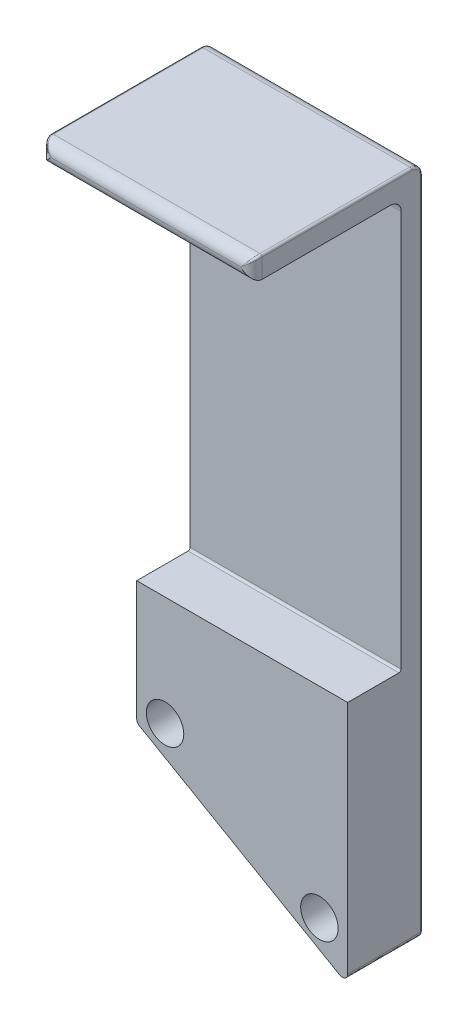
SolidWorks part; units mm, degrees
ref_plane "Front Plane" through (0, 0, 0) normal (0, 0, 1) x (1, 0, 0)
ref_plane "Top Plane" through (0, 0, 0) normal (0, 1, 0) x (1, 0, 0)
ref_plane "Right Plane" through (0, 0, 0) normal (1, 0, 0) x (0, 0, -1)
sketch "Model" plane through (0, 0, 0) normal (0, 0, 1) x (1, 0, 0)
  line L0 (-21.8431, 7.4481) -> (-8.6148, 30.3792)
  line L1 (-38.0636, 15.3297) -> (-23.771, 7.0696)
  line L2 (-75.3888, 20.2293) -> (-38.7189, 15.4592)
  line L3 (-86.2854, 34.8343) -> (-75.7419, 20.3766)
  line L4 (-29.1405, 92.9799) -> (-29.1405, 91.7303)
  line L5 (-8.8891, 91.2299) -> (-28.6402, 91.2299)
  line L6 (-8.3888, 90.7295) -> (-8.3888, 31.2555)
  line L7 (-86.6385, 34.9791) -> (-141.6396, 34.9791)
  line L8 (-142.1399, 90.7295) -> (-142.1399, 35.4795)
  line L9 (-104.6394, 91.2299) -> (-141.6396, 91.2299)
  line L10 (-104.139, 95.4793) -> (-104.139, 91.7303)
  line L11 (-85.6402, 95.9797) -> (-103.6387, 95.9797)
  line L12 (-85.1399, 97.7297) -> (-85.1399, 96.4801)
  line L13 (-67.6393, 98.2301) -> (-84.6395, 98.2301)
  line L14 (-67.1389, 96.4801) -> (-67.1389, 97.7297)
  line L15 (-48.6401, 95.9797) -> (-66.6385, 95.9797)
  line L16 (-48.1397, 93.9807) -> (-48.1397, 95.4793)
  line L17 (-29.6384, 93.4803) -> (-47.6393, 93.4803)
  line L18 (135.1563, 30.6526) -> (116.2359, 41.5721)
  line L19 (123.1828, 7.2669) -> (135.5373, 28.7222)
  line L20 (106.9623, 15.1485) -> (121.2549, 6.8884)
  line L21 (69.6371, 20.0481) -> (106.307, 15.278)
  line L22 (58.7405, 34.6531) -> (69.284, 20.1955)
  line L23 (115.8854, 92.7987) -> (115.8828, 42.2376)
  line L24 (58.3874, 34.7979) -> (3.3863, 34.7979)
  line L25 (2.886, 90.5483) -> (2.886, 35.2983)
  line L26 (40.3865, 91.0487) -> (3.3863, 91.0487)
  line L27 (40.8869, 95.2981) -> (40.8869, 91.5491)
  line L28 (59.3857, 95.7985) -> (41.3872, 95.7985)
  line L29 (59.886, 97.5485) -> (59.886, 96.2989)
  line L30 (77.3866, 98.0489) -> (60.3864, 98.0489)
  line L31 (77.887, 96.2989) -> (77.887, 97.5485)
  line L32 (96.3858, 95.7985) -> (78.3874, 95.7985)
  line L33 (96.8862, 93.7995) -> (96.8862, 95.2981)
  line L34 (115.3875, 93.2991) -> (97.3866, 93.2991)
  line L35 (20.1915, -96.2476) -> (6.9631, -73.3165)
  line L36 (36.4119, -88.366) -> (22.1193, -96.6261)
  line L37 (73.7371, -83.4663) -> (37.0672, -88.2365)
  line L38 (84.6337, -68.8614) -> (74.0902, -83.319)
  line L39 (27.4889, -10.7157) -> (27.4889, -11.9654)
  line L40 (7.2375, -12.4658) -> (26.9885, -12.4658)
  line L41 (6.7371, -12.9662) -> (6.7371, -72.4402)
  line L42 (84.9868, -68.7166) -> (139.9879, -68.7166)
  line L43 (140.4883, -12.9662) -> (140.4883, -68.2162)
  line L44 (102.9878, -12.4658) -> (139.9879, -12.4658)
  line L45 (102.4874, -8.2164) -> (102.4874, -11.9654)
  line L46 (83.9886, -7.716) -> (101.987, -7.716)
  line L47 (83.4882, -5.9659) -> (83.4882, -7.2156)
  line L48 (65.9876, -5.4656) -> (82.9878, -5.4656)
  line L49 (65.4872, -7.2156) -> (65.4872, -5.9659)
  line L50 (46.9884, -7.716) -> (64.9869, -7.716)
  line L51 (46.488, -9.715) -> (46.488, -8.2164)
  line L52 (27.9867, -10.2154) -> (45.9877, -10.2154)
  line L53 (-136.808, -73.043) -> (-117.8876, -62.1236)
  line L54 (-124.8344, -96.4288) -> (-137.189, -74.9734)
  line L55 (-108.614, -88.5472) -> (-122.9066, -96.8073)
  line L56 (-71.2888, -83.6475) -> (-107.9587, -88.4176)
  line L57 (-60.3922, -69.0425) -> (-70.9357, -83.5002)
  line L58 (-117.537, -10.8969) -> (-117.5345, -61.4581)
  line L59 (-60.0391, -68.8978) -> (-5.038, -68.8978)
  line L60 (-4.5376, -13.1474) -> (-4.5376, -68.3974)
  line L61 (-42.0381, -12.647) -> (-5.038, -12.647)
  line L62 (-42.5385, -8.3976) -> (-42.5385, -12.1466)
  line L63 (-61.0373, -7.8972) -> (-43.0389, -7.8972)
  line L64 (-61.5377, -6.1471) -> (-61.5377, -7.3968)
  line L65 (-79.0383, -5.6467) -> (-62.0381, -5.6467)
  line L66 (-79.5387, -7.3968) -> (-79.5387, -6.1471)
  line L67 (-98.0375, -7.8972) -> (-80.039, -7.8972)
  line L68 (-98.5378, -9.8962) -> (-98.5378, -8.3976)
  line L69 (-117.0392, -10.3965) -> (-99.0382, -10.3965)
  line L70 (138.9148, 92.1117) -> (138.9148, 33.3582)
  line L71 (138.1649, 32.9251) -> (119.446, 43.7282)
  line L72 (119.196, 44.1613) -> (119.196, 92.1092)
  line L73 (119.6959, 92.6092) -> (138.4148, 92.6117)
  line L74 (-140.5665, -11.584) -> (-140.5665, -70.3375)
  line L75 (-139.8166, -70.7706) -> (-121.0977, -59.9674)
  line L76 (-120.8476, -59.5344) -> (-120.8476, -11.5865)
  line L77 (-121.3476, -11.0865) -> (-140.0664, -11.084)
  line L78 (18.8966, 74.9256) -> (4.8966, 74.9256)
  line L79 (4.8966, 74.9256) -> (4.8966, 88.9256)
  line L80 (4.8966, 88.9256) -> (18.8966, 88.9256)
  line L81 (18.8966, 88.9256) -> (18.8966, 74.9256)
  line L82 (18.8966, 55.9256) -> (4.8966, 55.9256)
  line L83 (4.8966, 55.9256) -> (4.8966, 69.9256)
  line L84 (4.8966, 69.9256) -> (18.8966, 69.9256)
  line L85 (18.8966, 69.9256) -> (18.8966, 55.9256)
  line L86 (18.8966, 36.9256) -> (4.8966, 36.9256)
  line L87 (4.8966, 36.9256) -> (4.8966, 50.9256)
  line L88 (4.8966, 50.9256) -> (18.8966, 50.9256)
  line L89 (18.8966, 50.9256) -> (18.8966, 36.9256)
  line L90 (37.8948, 74.9262) -> (23.8948, 74.9262)
  line L91 (23.8948, 74.9262) -> (23.8948, 88.9262)
  line L92 (23.8948, 88.9262) -> (37.8948, 88.9262)
  line L93 (37.8948, 88.9262) -> (37.8948, 74.9262)
  line L94 (37.8948, 55.9262) -> (23.8948, 55.9262)
  line L95 (23.8948, 55.9262) -> (23.8948, 69.9262)
  line L96 (23.8948, 69.9262) -> (37.8948, 69.9262)
  line L97 (37.8948, 69.9262) -> (37.8948, 55.9262)
  line L98 (37.8948, 36.9262) -> (23.8948, 36.9262)
  line L99 (23.8948, 36.9262) -> (23.8948, 50.9262)
  line L100 (23.8948, 50.9262) -> (37.8948, 50.9262)
  line L101 (37.8948, 50.9262) -> (37.8948, 36.9262)
  line L102 (56.895, 79.671) -> (42.895, 79.671)
  line L103 (42.895, 79.671) -> (42.895, 93.671)
  line L104 (42.895, 93.671) -> (56.895, 93.671)
  line L105 (56.895, 93.671) -> (56.895, 79.671)
  line L106 (56.895, 60.6711) -> (42.895, 60.6711)
  line L107 (42.895, 60.6711) -> (42.895, 74.6711)
  line L108 (42.895, 74.6711) -> (56.895, 74.6711)
  line L109 (56.895, 74.6711) -> (56.895, 60.6711)
  line L110 (56.895, 41.6711) -> (42.895, 41.6711)
  line L111 (42.895, 41.6711) -> (42.895, 55.6711)
  line L112 (42.895, 55.6711) -> (56.895, 55.6711)
  line L113 (56.895, 55.6711) -> (56.895, 41.6711)
  line L114 (75.897, 82.0499) -> (61.897, 82.0499)
  line L115 (61.897, 82.0499) -> (61.897, 96.0499)
  line L116 (61.897, 96.0499) -> (75.897, 96.0499)
  line L117 (75.897, 96.0499) -> (75.897, 82.0499)
  line L118 (75.897, 63.0499) -> (61.897, 63.0499)
  line L119 (61.897, 63.0499) -> (61.897, 77.0499)
  line L120 (61.897, 77.0499) -> (75.897, 77.0499)
  line L121 (75.897, 77.0499) -> (75.897, 63.0499)
  line L122 (75.897, 44.0499) -> (61.897, 44.0499)
  line L123 (61.897, 44.0499) -> (61.897, 58.0499)
  line L124 (61.897, 58.0499) -> (75.897, 58.0499)
  line L125 (75.897, 58.0499) -> (75.897, 44.0499)
  line L126 (94.8982, 79.6753) -> (80.8982, 79.6753)
  line L127 (80.8982, 79.6753) -> (80.8982, 93.6753)
  line L128 (80.8982, 93.6753) -> (94.8982, 93.6753)
  line L129 (94.8982, 93.6753) -> (94.8982, 79.6753)
  line L130 (94.8982, 60.6753) -> (80.8982, 60.6753)
  line L131 (80.8982, 60.6753) -> (80.8982, 74.6753)
  line L132 (80.8982, 74.6753) -> (94.8982, 74.6753)
  line L133 (94.8982, 74.6753) -> (94.8982, 60.6753)
  line L134 (94.8982, 41.6753) -> (80.8982, 41.6753)
  line L135 (80.8982, 41.6753) -> (80.8982, 55.6753)
  line L136 (80.8982, 55.6753) -> (94.8982, 55.6753)
  line L137 (94.8982, 55.6753) -> (94.8982, 41.6753)
  line L138 (113.9, 77.2905) -> (99.9, 77.2905)
  line L139 (99.9, 77.2905) -> (99.9, 91.2905)
  line L140 (99.9, 91.2905) -> (113.9, 91.2905)
  line L141 (113.9, 91.2905) -> (113.9, 77.2905)
  line L142 (113.9, 58.2905) -> (99.9, 58.2905)
  line L143 (99.9, 58.2905) -> (99.9, 72.2905)
  line L144 (99.9, 72.2905) -> (113.9, 72.2905)
  line L145 (113.9, 72.2905) -> (113.9, 58.2905)
  line L146 (113.9, 39.2905) -> (99.9, 39.2905)
  line L147 (99.9, 39.2905) -> (99.9, 53.2905)
  line L148 (99.9, 53.2905) -> (113.9, 53.2905)
  line L149 (113.9, 53.2905) -> (113.9, 39.2905)
  line L150 (85.4166, 22.0174) -> (71.4166, 22.0174)
  line L151 (71.4166, 22.0174) -> (71.4166, 36.0174)
  line L152 (71.4166, 36.0174) -> (85.4166, 36.0174)
  line L153 (85.4166, 36.0174) -> (85.4166, 22.0174)
  line L154 (104.3289, 17.734) -> (90.806, 21.3575)
  line L155 (90.806, 21.3575) -> (94.4294, 34.8805)
  line L156 (94.4294, 34.8805) -> (107.9524, 31.257)
  line L157 (107.9524, 31.257) -> (104.3289, 17.734)
  line L158 (124.1994, 13.0049) -> (112.075, 20.0049)
  line L159 (112.075, 20.0049) -> (119.075, 32.1293)
  line L160 (119.075, 32.1293) -> (131.1994, 25.1293)
  line L161 (131.1994, 25.1293) -> (124.1994, 13.0049)
  line L162 (-20.5483, -28.7701) -> (-6.5483, -28.7701)
  line L163 (-6.5483, -28.7701) -> (-6.5483, -14.7701)
  line L164 (-6.5483, -14.7701) -> (-20.5483, -14.7701)
  line L165 (-20.5483, -14.7701) -> (-20.5483, -28.7701)
  line L166 (-20.5483, -47.7701) -> (-6.5483, -47.7701)
  line L167 (-6.5483, -47.7701) -> (-6.5483, -33.7701)
  line L168 (-6.5483, -33.7701) -> (-20.5483, -33.7701)
  line L169 (-20.5483, -33.7701) -> (-20.5483, -47.7701)
  line L170 (-20.5483, -66.7701) -> (-6.5483, -66.7701)
  line L171 (-6.5483, -66.7701) -> (-6.5483, -52.7701)
  line L172 (-6.5483, -52.7701) -> (-20.5483, -52.7701)
  line L173 (-20.5483, -52.7701) -> (-20.5483, -66.7701)
  line L174 (-39.5464, -28.7694) -> (-25.5464, -28.7694)
  line L175 (-25.5464, -28.7694) -> (-25.5464, -14.7694)
  line L176 (-25.5464, -14.7694) -> (-39.5464, -14.7694)
  line L177 (-39.5464, -14.7694) -> (-39.5464, -28.7694)
  line L178 (-39.5464, -47.7694) -> (-25.5464, -47.7694)
  line L179 (-25.5464, -47.7694) -> (-25.5464, -33.7694)
  line L180 (-25.5464, -33.7694) -> (-39.5464, -33.7694)
  line L181 (-39.5464, -33.7694) -> (-39.5464, -47.7694)
  line L182 (-39.5464, -66.7694) -> (-25.5464, -66.7694)
  line L183 (-25.5464, -66.7694) -> (-25.5464, -52.7694)
  line L184 (-25.5464, -52.7694) -> (-39.5464, -52.7694)
  line L185 (-39.5464, -52.7694) -> (-39.5464, -66.7694)
  line L186 (-58.5467, -24.0246) -> (-44.5467, -24.0246)
  line L187 (-44.5467, -24.0246) -> (-44.5467, -10.0246)
  line L188 (-44.5467, -10.0246) -> (-58.5467, -10.0246)
  line L189 (-58.5467, -10.0246) -> (-58.5467, -24.0246)
  line L190 (-58.5467, -43.0246) -> (-44.5467, -43.0246)
  line L191 (-44.5467, -43.0246) -> (-44.5467, -29.0246)
  line L192 (-44.5467, -29.0246) -> (-58.5467, -29.0246)
  line L193 (-58.5467, -29.0246) -> (-58.5467, -43.0246)
  line L194 (-58.5467, -62.0246) -> (-44.5467, -62.0246)
  line L195 (-44.5467, -62.0246) -> (-44.5467, -48.0246)
  line L196 (-44.5467, -48.0246) -> (-58.5467, -48.0246)
  line L197 (-58.5467, -48.0246) -> (-58.5467, -62.0246)
  line L198 (-77.5486, -21.6458) -> (-63.5486, -21.6458)
  line L199 (-63.5486, -21.6458) -> (-63.5486, -7.6458)
  line L200 (-63.5486, -7.6458) -> (-77.5486, -7.6458)
  line L201 (-77.5486, -7.6458) -> (-77.5486, -21.6458)
  line L202 (-77.5486, -40.6458) -> (-63.5486, -40.6458)
  line L203 (-63.5486, -40.6458) -> (-63.5486, -26.6458)
  line L204 (-63.5486, -26.6458) -> (-77.5486, -26.6458)
  line L205 (-77.5486, -26.6458) -> (-77.5486, -40.6458)
  line L206 (-77.5486, -59.6458) -> (-63.5486, -59.6458)
  line L207 (-63.5486, -59.6458) -> (-63.5486, -45.6458)
  line L208 (-63.5486, -45.6458) -> (-77.5486, -45.6458)
  line L209 (-77.5486, -45.6458) -> (-77.5486, -59.6458)
  line L210 (-96.5499, -24.0204) -> (-82.5499, -24.0204)
  line L211 (-82.5499, -24.0204) -> (-82.5499, -10.0204)
  line L212 (-82.5499, -10.0204) -> (-96.5499, -10.0204)
  line L213 (-96.5499, -10.0204) -> (-96.5499, -24.0204)
  line L214 (-96.5499, -43.0203) -> (-82.5499, -43.0203)
  line L215 (-82.5499, -43.0203) -> (-82.5499, -29.0203)
  line L216 (-82.5499, -29.0203) -> (-96.5499, -29.0203)
  line L217 (-96.5499, -29.0203) -> (-96.5499, -43.0203)
  line L218 (-96.5499, -62.0203) -> (-82.5499, -62.0203)
  line L219 (-82.5499, -62.0203) -> (-82.5499, -48.0203)
  line L220 (-82.5499, -48.0203) -> (-96.5499, -48.0203)
  line L221 (-96.5499, -48.0203) -> (-96.5499, -62.0203)
  line L222 (-115.5516, -26.4052) -> (-101.5516, -26.4052)
  line L223 (-101.5516, -26.4052) -> (-101.5516, -12.4052)
  line L224 (-101.5516, -12.4052) -> (-115.5516, -12.4052)
  line L225 (-115.5516, -12.4052) -> (-115.5516, -26.4052)
  line L226 (-115.5516, -45.4052) -> (-101.5516, -45.4052)
  line L227 (-101.5516, -45.4052) -> (-101.5516, -31.4052)
  line L228 (-101.5516, -31.4052) -> (-115.5516, -31.4052)
  line L229 (-115.5516, -31.4052) -> (-115.5516, -45.4052)
  line L230 (-115.5516, -64.4052) -> (-101.5516, -64.4052)
  line L231 (-101.5516, -64.4052) -> (-101.5516, -50.4052)
  line L232 (-101.5516, -50.4052) -> (-115.5516, -50.4052)
  line L233 (-115.5516, -50.4052) -> (-115.5516, -64.4052)
  line L234 (-87.0683, -81.6783) -> (-73.0683, -81.6783)
  line L235 (-73.0683, -81.6783) -> (-73.0683, -67.6783)
  line L236 (-73.0683, -67.6783) -> (-87.0683, -67.6783)
  line L237 (-87.0683, -67.6783) -> (-87.0683, -81.6783)
  line L238 (-105.9806, -85.9616) -> (-92.4576, -82.3382)
  line L239 (-92.4576, -82.3382) -> (-96.0811, -68.8152)
  line L240 (-96.0811, -68.8152) -> (-109.6041, -72.4387)
  line L241 (-109.6041, -72.4387) -> (-105.9806, -85.9616)
  line L242 (-125.851, -90.6908) -> (-113.7267, -83.6908)
  line L243 (-113.7267, -83.6908) -> (-120.7267, -71.5664)
  line L244 (-120.7267, -71.5664) -> (-132.851, -78.5664)
  line L245 (-132.851, -78.5664) -> (-125.851, -90.6908)
  spline S0 degree 3 poles (-8.6153, 30.3807) (-8.4626, 30.6458) (-8.3842, 30.9472) (-8.3882, 31.2532) knots 0 0 0 0 1 1 1 1
  spline S1 degree 3 poles (-21.8439, 7.4422) (-21.8429, 7.4437) (-21.8419, 7.4453) (-21.8408, 7.4468) knots 1 1 1 1 2 2 2 2
  spline S2 degree 3 poles (-23.769, 7.0673) (-23.1339, 6.6392) (-22.272, 6.8071) (-21.8439, 7.4422) knots 0 0 0 0 1 1 1 1
  spline S3 degree 3 poles (-38.063, 15.3284) (-38.2765, 15.3928) (-38.4957, 15.4362) (-38.7176, 15.4579) knots 0 0 0 0 1 1 1 1
  spline S4 degree 3 poles (-75.7416, 20.3746) (-75.6478, 20.2809) (-75.5206, 20.2283) (-75.3881, 20.2283) knots 0 0 0 0 1 1 1 1
  spline S5 degree 3 poles (-29.1383, 92.9782) (-29.1382, 93.2543) (-29.362, 93.4782) (-29.6381, 93.4783) knots 0 0 0 0 1 1 1 1
  spline S6 degree 3 poles (-29.1383, 91.7282) (-29.1383, 91.4521) (-28.9145, 91.2282) (-28.6384, 91.2281) (-28.6383, 91.2281) (-28.6382, 91.2281) (-28.6381, 91.2281) knots 0 0 0 0 1 1 1 2 2 2 2
  spline S7 degree 3 poles (-86.2846, 34.8318) (-86.3784, 34.9256) (-86.5056, 34.9783) (-86.6385, 34.9791) knots 0 0 0 0 1 1 1 1
  spline S8 degree 3 poles (-142.1382, 35.4782) (-142.1381, 35.2021) (-141.9142, 34.9783) (-141.6381, 34.9783) knots 0 0 0 0 1 1 1 1
  spline S9 degree 3 poles (-141.638, 91.2281) (-141.9142, 91.2282) (-142.1381, 91.0044) (-142.1382, 90.7282) knots 0 0 0 0 1 1 1 1
  spline S10 degree 3 poles (-104.6382, 91.2281) (-104.362, 91.228) (-104.1381, 91.4518) (-104.138, 91.728) (-104.138, 91.7281) (-104.138, 91.7281) (-104.138, 91.7282) knots 0 0 0 0 1 1 1 2 2 2 2
  spline S11 degree 3 poles (-103.6382, 95.9781) (-103.9142, 95.9781) (-104.138, 95.7543) (-104.138, 95.4783) knots 0 0 0 0 1 1 1 1
  spline S12 degree 3 poles (-85.6382, 95.9781) (-85.3621, 95.9781) (-85.1382, 96.2019) (-85.1381, 96.478) (-85.1381, 96.4781) (-85.1381, 96.4782) (-85.1381, 96.4783) knots 0 0 0 0 1 1 1 2 2 2 2
  spline S13 degree 3 poles (-84.6382, 98.2283) (-84.9144, 98.2283) (-85.1382, 98.0044) (-85.1381, 97.7282) knots 0 0 0 0 1 1 1 1
  spline S14 degree 3 poles (-67.1381, 97.7282) (-67.1381, 98.0043) (-67.3619, 98.2283) (-67.638, 98.2283) knots 0 0 0 0 2 2 2 2
  spline S15 degree 3 poles (-67.1381, 96.4783) (-67.1382, 96.2021) (-66.9144, 95.9782) (-66.6383, 95.9781) (-66.6382, 95.9781) (-66.6381, 95.9781) (-66.638, 95.9781) knots 0 0 0 0 1 1 1 2 2 2 2
  spline S16 degree 3 poles (-48.1382, 95.4783) (-48.1383, 95.7543) (-48.362, 95.9781) (-48.6381, 95.9781) knots 0 0 0 0 1 1 1 1
  spline S17 degree 3 poles (-48.1382, 93.9782) (-48.1381, 93.702) (-47.9142, 93.4782) (-47.6381, 93.4783) knots 0 0 0 0 1 1 1 1
  spline S18 degree 3 poles (-8.3882, 90.7282) (-8.3883, 91.0043) (-8.6121, 91.228) (-8.8881, 91.2281) knots 0 0 0 0 1 1 1 1
  spline S19 degree 3 poles (115.8851, 42.2368) (115.8929, 41.9725) (116.0232, 41.7268) (116.2377, 41.5721) knots 0 0 0 0 1 1 1 1
  spline S20 degree 3 poles (135.163, 30.647) (135.1614, 30.648) (135.1599, 30.6491) (135.1583, 30.6501) knots 1 1 1 1 2 2 2 2
  spline S21 degree 3 poles (135.5373, 28.7222) (135.9659, 29.3571) (135.7981, 30.2189) (135.163, 30.647) knots 0 0 0 0 1 1 1 1
  spline S22 degree 3 poles (123.182, 7.261) (123.183, 7.2625) (123.184, 7.2641) (123.1851, 7.2656) knots 1 1 1 1 2 2 2 2
  spline S23 degree 3 poles (121.2569, 6.8861) (121.892, 6.4581) (122.7539, 6.6259) (123.182, 7.261) knots 0 0 0 0 1 1 1 1
  spline S24 degree 3 poles (106.9629, 15.1472) (106.7494, 15.2117) (106.5302, 15.255) (106.3083, 15.2768) knots 0 0 0 0 1 1 1 1
  spline S25 degree 3 poles (69.2843, 20.1934) (69.3781, 20.0997) (69.5053, 20.0471) (69.6378, 20.0471) knots 0 0 0 0 1 1 1 1
  spline S26 degree 3 poles (115.8876, 92.797) (115.8877, 93.0731) (115.6639, 93.297) (115.3878, 93.2971) knots 0 0 0 0 1 1 1 1
  spline S27 degree 3 poles (58.7413, 34.6506) (58.6475, 34.7444) (58.5203, 34.7971) (58.3874, 34.7979) knots 0 0 0 0 1 1 1 1
  spline S28 degree 3 poles (2.8877, 35.297) (2.8878, 35.0209) (3.1117, 34.7971) (3.3878, 34.7971) knots 0 0 0 0 1 1 1 1
  spline S29 degree 3 poles (3.3879, 91.0469) (3.1117, 91.047) (2.8878, 90.8232) (2.8877, 90.547) knots 0 0 0 0 1 1 1 1
  spline S30 degree 3 poles (40.3877, 91.0469) (40.6639, 91.0468) (40.8878, 91.2706) (40.8879, 91.5468) (40.8879, 91.5469) (40.8879, 91.5469) (40.8879, 91.547) knots 0 0 0 0 1 1 1 2 2 2 2
  spline S31 degree 3 poles (41.3877, 95.797) (41.1117, 95.7969) (40.8879, 95.5731) (40.8879, 95.2971) knots 0 0 0 0 1 1 1 1
  spline S32 degree 3 poles (59.3877, 95.797) (59.6638, 95.7969) (59.8877, 96.0207) (59.8878, 96.2968) (59.8878, 96.2969) (59.8878, 96.297) (59.8878, 96.2971) knots 0 0 0 0 1 1 1 2 2 2 2
  spline S33 degree 3 poles (60.3877, 98.0471) (60.1115, 98.0471) (59.8877, 97.8232) (59.8878, 97.547) knots 0 0 0 0 1 1 1 1
  spline S34 degree 3 poles (77.8878, 97.547) (77.8878, 97.8232) (77.664, 98.0471) (77.3879, 98.0471) knots 0 0 0 0 2 2 2 2
  spline S35 degree 3 poles (77.8878, 96.2971) (77.8877, 96.0209) (78.1115, 95.797) (78.3876, 95.797) (78.3877, 95.797) (78.3878, 95.797) (78.3879, 95.797) knots 0 0 0 0 1 1 1 2 2 2 2
  spline S36 degree 3 poles (96.8877, 95.2971) (96.8876, 95.5731) (96.6639, 95.7969) (96.3878, 95.797) knots 0 0 0 0 1 1 1 1
  spline S37 degree 3 poles (96.8877, 93.797) (96.8878, 93.5208) (97.1117, 93.297) (97.3878, 93.2971) knots 0 0 0 0 1 1 1 1
  spline S38 degree 3 poles (6.9637, -73.315) (6.8109, -73.0499) (6.7325, -72.7484) (6.7366, -72.4425) knots 0 0 0 0 1 1 1 1
  spline S39 degree 3 poles (20.1923, -96.2535) (20.1912, -96.252) (20.1902, -96.2504) (20.1892, -96.2489) knots 1 1 1 1 2 2 2 2
  spline S40 degree 3 poles (22.1173, -96.6284) (21.4822, -97.0564) (20.6203, -96.8886) (20.1923, -96.2535) knots 0 0 0 0 1 1 1 1
  spline S41 degree 3 poles (36.4114, -88.3673) (36.6248, -88.3028) (36.844, -88.2594) (37.0659, -88.2377) knots 0 0 0 0 1 1 1 1
  spline S42 degree 3 poles (74.0899, -83.3211) (73.9962, -83.4148) (73.869, -83.4674) (73.7364, -83.4674) knots 0 0 0 0 1 1 1 1
  spline S43 degree 3 poles (27.4866, -10.7175) (27.4865, -10.4414) (27.7103, -10.2175) (27.9865, -10.2174) knots 0 0 0 0 1 1 1 1
  spline S44 degree 3 poles (27.4866, -11.9674) (27.4866, -12.2436) (27.2628, -12.4675) (26.9867, -12.4676) (26.9866, -12.4676) (26.9865, -12.4676) (26.9865, -12.4676) knots 0 0 0 0 1 1 1 2 2 2 2
  spline S45 degree 3 poles (84.633, -68.8639) (84.7267, -68.7701) (84.8539, -68.7174) (84.9868, -68.7166) knots 0 0 0 0 1 1 1 1
  spline S46 degree 3 poles (140.4865, -68.2175) (140.4864, -68.4936) (140.2625, -68.7174) (139.9864, -68.7173) knots 0 0 0 0 1 1 1 1
  spline S47 degree 3 poles (139.9864, -12.4676) (140.2625, -12.4675) (140.4864, -12.6913) (140.4865, -12.9674) knots 0 0 0 0 1 1 1 1
  spline S48 degree 3 poles (102.9865, -12.4676) (102.7103, -12.4676) (102.4864, -12.2438) (102.4864, -11.9677) (102.4864, -11.9676) (102.4864, -11.9675) (102.4864, -11.9674) knots 0 0 0 0 1 1 1 2 2 2 2
  spline S49 degree 3 poles (101.9865, -7.7175) (102.2625, -7.7176) (102.4863, -7.9413) (102.4864, -8.2174) knots 0 0 0 0 1 1 1 1
  spline S50 degree 3 poles (83.9865, -7.7175) (83.7104, -7.7176) (83.4865, -7.4938) (83.4864, -7.2176) (83.4864, -7.2176) (83.4864, -7.2175) (83.4864, -7.2174) knots 0 0 0 0 1 1 1 2 2 2 2
  spline S51 degree 3 poles (82.9865, -5.4673) (83.2627, -5.4674) (83.4865, -5.6913) (83.4864, -5.9675) knots 0 0 0 0 1 1 1 1
  spline S52 degree 3 poles (65.4865, -5.9675) (65.4864, -5.6913) (65.7102, -5.4674) (65.9863, -5.4673) knots 0 0 0 0 2 2 2 2
  spline S53 degree 3 poles (65.4865, -7.2174) (65.4865, -7.4935) (65.2627, -7.7174) (64.9866, -7.7175) (64.9865, -7.7175) (64.9864, -7.7175) (64.9863, -7.7175) knots 0 0 0 0 1 1 1 2 2 2 2
  spline S54 degree 3 poles (46.4865, -8.2174) (46.4866, -7.9413) (46.7103, -7.7176) (46.9864, -7.7175) knots 0 0 0 0 1 1 1 1
  spline S55 degree 3 poles (46.4865, -9.7175) (46.4865, -9.9937) (46.2625, -10.2175) (45.9864, -10.2174) knots 0 0 0 0 1 1 1 1
  spline S56 degree 3 poles (6.7366, -12.9674) (6.7366, -12.6914) (6.9604, -12.4676) (7.2365, -12.4676) knots 0 0 0 0 1 1 1 1
  spline S57 degree 3 poles (-117.5368, -61.4589) (-117.5446, -61.7232) (-117.6748, -61.9689) (-117.8893, -62.1236) knots 0 0 0 0 1 1 1 1
  spline S58 degree 3 poles (-136.8146, -73.0487) (-136.8131, -73.0476) (-136.8116, -73.0466) (-136.81, -73.0456) knots 1 1 1 1 2 2 2 2
  spline S59 degree 3 poles (-137.189, -74.9734) (-137.6176, -74.3386) (-137.4497, -73.4767) (-136.8146, -73.0487) knots 0 0 0 0 1 1 1 1
  spline S60 degree 3 poles (-124.8336, -96.4347) (-124.8347, -96.4331) (-124.8357, -96.4316) (-124.8367, -96.4301) knots 1 1 1 1 2 2 2 2
  spline S61 degree 3 poles (-122.9086, -96.8095) (-123.5437, -97.2376) (-124.4056, -97.0698) (-124.8336, -96.4347) knots 0 0 0 0 1 1 1 1
  spline S62 degree 3 poles (-108.6145, -88.5485) (-108.4011, -88.484) (-108.1819, -88.4406) (-107.96, -88.4189) knots 0 0 0 0 1 1 1 1
  spline S63 degree 3 poles (-70.936, -83.5022) (-71.0297, -83.596) (-71.1569, -83.6486) (-71.2895, -83.6485) knots 0 0 0 0 1 1 1 1
  spline S64 degree 3 poles (-117.5393, -10.8987) (-117.5394, -10.6226) (-117.3156, -10.3987) (-117.0394, -10.3986) knots 0 0 0 0 1 1 1 1
  spline S65 degree 3 poles (-60.3929, -69.0451) (-60.2992, -68.9513) (-60.172, -68.8986) (-60.0391, -68.8978) knots 0 0 0 0 1 1 1 1
  spline S66 degree 3 poles (-4.5394, -68.3987) (-4.5395, -68.6748) (-4.7634, -68.8986) (-5.0395, -68.8985) knots 0 0 0 0 1 1 1 1
  spline S67 degree 3 poles (-5.0395, -12.6488) (-4.7634, -12.6487) (-4.5395, -12.8725) (-4.5394, -13.1486) knots 0 0 0 0 1 1 1 1
  spline S68 degree 3 poles (-42.0394, -12.6488) (-42.3156, -12.6488) (-42.5395, -12.425) (-42.5395, -12.1489) (-42.5395, -12.1488) (-42.5395, -12.1487) (-42.5395, -12.1486) knots 0 0 0 0 1 1 1 2 2 2 2
  spline S69 degree 3 poles (-43.0394, -7.8987) (-42.7634, -7.8988) (-42.5396, -8.1225) (-42.5395, -8.3986) knots 0 0 0 0 1 1 1 1
  spline S70 degree 3 poles (-61.0394, -7.8987) (-61.3155, -7.8988) (-61.5394, -7.675) (-61.5395, -7.3988) (-61.5395, -7.3988) (-61.5395, -7.3987) (-61.5395, -7.3986) knots 0 0 0 0 1 1 1 2 2 2 2
  spline S71 degree 3 poles (-62.0394, -5.6485) (-61.7632, -5.6486) (-61.5394, -5.8725) (-61.5395, -6.1486) knots 0 0 0 0 1 1 1 1
  spline S72 degree 3 poles (-79.5394, -6.1486) (-79.5395, -5.8725) (-79.3157, -5.6486) (-79.0396, -5.6485) knots 0 0 0 0 2 2 2 2
  spline S73 degree 3 poles (-79.5394, -7.3986) (-79.5394, -7.6747) (-79.7632, -7.8986) (-80.0393, -7.8987) (-80.0394, -7.8987) (-80.0395, -7.8987) (-80.0396, -7.8987) knots 0 0 0 0 1 1 1 2 2 2 2
  spline S74 degree 3 poles (-98.5394, -8.3986) (-98.5393, -8.1225) (-98.3156, -7.8988) (-98.0395, -7.8987) knots 0 0 0 0 1 1 1 1
  spline S75 degree 3 poles (-98.5394, -9.8987) (-98.5394, -10.1748) (-98.7634, -10.3986) (-99.0395, -10.3986) knots 0 0 0 0 1 1 1 1
  spline S76 degree 3 poles (-123.6381, 52.6314) (-124.2456, 52.6314) (-124.7381, 53.1239) (-124.7381, 53.7314) (-124.7381, 54.3389) (-124.2456, 54.8314) (-123.6381, 54.8314) knots 2 2 2 2 3 3 3 4 4 4 4
  spline S77 degree 3 poles (-123.6381, 54.8314) (-123.0306, 54.8314) (-122.5381, 54.3389) (-122.5381, 53.7314) (-122.5381, 53.1239) (-123.0306, 52.6314) (-123.6381, 52.6314) knots 0 0 0 0 1 1 1 2 2 2 2
  spline S78 degree 3 poles (-123.6381, 71.3814) (-124.2456, 71.3814) (-124.7381, 71.8739) (-124.7381, 72.4814) (-124.7381, 73.0889) (-124.2456, 73.5814) (-123.6381, 73.5814) knots 2 2 2 2 3 3 3 4 4 4 4
  spline S79 degree 3 poles (-123.6381, 73.5814) (-123.0306, 73.5814) (-122.5381, 73.0889) (-122.5381, 72.4814) (-122.5381, 71.8739) (-123.0306, 71.3814) (-123.6381, 71.3814) knots 0 0 0 0 1 1 1 2 2 2 2
  spline S80 degree 3 poles (-47.6381, 75.1312) (-48.2456, 75.1312) (-48.7381, 75.6237) (-48.7381, 76.2312) (-48.7381, 76.8387) (-48.2456, 77.3312) (-47.6381, 77.3312) knots 2 2 2 2 3 3 3 4 4 4 4
  spline S81 degree 3 poles (-47.6381, 77.3312) (-47.0306, 77.3312) (-46.5381, 76.8387) (-46.5381, 76.2312) (-46.5381, 75.6237) (-47.0306, 75.1312) (-47.6381, 75.1312) knots 0 0 0 0 1 1 1 2 2 2 2
  spline S82 degree 3 poles (-80.388, 35.3813) (-80.9956, 35.3813) (-81.488, 35.8738) (-81.488, 36.4813) (-81.488, 37.0888) (-80.9956, 37.5813) (-80.388, 37.5813) knots 2 2 2 2 3 3 3 4 4 4 4
  spline S83 degree 3 poles (-80.388, 37.5813) (-79.7805, 37.5813) (-79.288, 37.0888) (-79.288, 36.4813) (-79.288, 35.8738) (-79.7805, 35.3813) (-80.388, 35.3813) knots 0 0 0 0 1 1 1 2 2 2 2
  spline S84 degree 3 poles (-33.8881, 27.6312) (-34.4956, 27.6312) (-34.9881, 28.1237) (-34.9881, 28.7312) (-34.9881, 29.3388) (-34.4956, 29.8312) (-33.8881, 29.8312) knots 2 2 2 2 3 3 3 4 4 4 4
  spline S85 degree 3 poles (-33.8881, 29.8312) (-33.2805, 29.8312) (-32.7881, 29.3388) (-32.7881, 28.7312) (-32.7881, 28.1237) (-33.2805, 27.6312) (-33.8881, 27.6312) knots 0 0 0 0 1 1 1 2 2 2 2
  spline S86 degree 3 poles (21.3878, 52.4502) (20.7803, 52.4502) (20.2878, 52.9427) (20.2878, 53.5502) (20.2878, 54.1578) (20.7803, 54.6502) (21.3878, 54.6502) knots 2 2 2 2 3 3 3 4 4 4 4
  spline S87 degree 3 poles (21.3878, 54.6502) (21.9953, 54.6502) (22.4878, 54.1578) (22.4878, 53.5502) (22.4878, 52.9427) (21.9953, 52.4502) (21.3878, 52.4502) knots 0 0 0 0 1 1 1 2 2 2 2
  spline S88 degree 3 poles (97.3878, 74.95) (96.7803, 74.95) (96.2878, 75.4425) (96.2878, 76.05) (96.2878, 76.6575) (96.7803, 77.15) (97.3878, 77.15) knots 2 2 2 2 3 3 3 4 4 4 4
  spline S89 degree 3 poles (97.3878, 77.15) (97.9953, 77.15) (98.4878, 76.6575) (98.4878, 76.05) (98.4878, 75.4425) (97.9953, 74.95) (97.3878, 74.95) knots 0 0 0 0 1 1 1 2 2 2 2
  spline S90 degree 3 poles (64.6379, 35.2001) (64.0303, 35.2001) (63.5379, 35.6926) (63.5379, 36.3001) (63.5379, 36.9076) (64.0303, 37.4001) (64.6379, 37.4001) knots 2 2 2 2 3 3 3 4 4 4 4
  spline S91 degree 3 poles (64.6379, 37.4001) (65.2454, 37.4001) (65.7379, 36.9076) (65.7379, 36.3001) (65.7379, 35.6926) (65.2454, 35.2001) (64.6379, 35.2001) knots 0 0 0 0 1 1 1 2 2 2 2
  spline S92 degree 3 poles (111.1378, 27.4501) (110.5303, 27.4501) (110.0378, 27.9425) (110.0378, 28.5501) (110.0378, 29.1576) (110.5303, 29.65) (111.1378, 29.65) knots 2 2 2 2 3 3 3 4 4 4 4
  spline S93 degree 3 poles (111.1378, 29.65) (111.7454, 29.65) (112.2378, 29.1576) (112.2378, 28.5501) (112.2378, 27.9425) (111.7454, 27.4501) (111.1378, 27.4501) knots 0 0 0 0 1 1 1 2 2 2 2
  spline S94 degree 3 poles (121.9864, -51.0642) (122.5939, -51.0642) (123.0864, -50.5718) (123.0864, -49.9642) (123.0864, -49.3567) (122.5939, -48.8642) (121.9864, -48.8642) knots 2 2 2 2 3 3 3 4 4 4 4
  spline S95 degree 3 poles (121.9864, -48.8642) (121.3789, -48.8642) (120.8864, -49.3567) (120.8864, -49.9642) (120.8864, -50.5718) (121.3789, -51.0642) (121.9864, -51.0642) knots 0 0 0 0 1 1 1 2 2 2 2
  spline S96 degree 3 poles (121.9864, -32.3142) (122.5939, -32.3142) (123.0864, -31.8218) (123.0864, -31.2142) (123.0864, -30.6067) (122.5939, -30.1142) (121.9864, -30.1142) knots 2 2 2 2 3 3 3 4 4 4 4
  spline S97 degree 3 poles (121.9864, -30.1142) (121.3789, -30.1142) (120.8864, -30.6067) (120.8864, -31.2142) (120.8864, -31.8218) (121.3789, -32.3142) (121.9864, -32.3142) knots 0 0 0 0 1 1 1 2 2 2 2
  spline S98 degree 3 poles (45.9864, -28.5644) (46.5939, -28.5644) (47.0864, -28.072) (47.0864, -27.4644) (47.0864, -26.8569) (46.5939, -26.3644) (45.9864, -26.3644) knots 2 2 2 2 3 3 3 4 4 4 4
  spline S99 degree 3 poles (45.9864, -26.3644) (45.3789, -26.3644) (44.8864, -26.8569) (44.8864, -27.4644) (44.8864, -28.072) (45.3789, -28.5644) (45.9864, -28.5644) knots 0 0 0 0 1 1 1 2 2 2 2
  spline S100 degree 3 poles (78.7364, -68.3144) (79.3439, -68.3144) (79.8364, -67.8219) (79.8364, -67.2144) (79.8364, -66.6069) (79.3439, -66.1144) (78.7364, -66.1144) knots 2 2 2 2 3 3 3 4 4 4 4
  spline S101 degree 3 poles (78.7364, -66.1144) (78.1288, -66.1144) (77.6364, -66.6069) (77.6364, -67.2144) (77.6364, -67.8219) (78.1288, -68.3144) (78.7364, -68.3144) knots 0 0 0 0 1 1 1 2 2 2 2
  spline S102 degree 3 poles (32.2364, -76.0644) (32.8439, -76.0644) (33.3364, -75.5719) (33.3364, -74.9644) (33.3364, -74.3569) (32.8439, -73.8644) (32.2364, -73.8644) knots 2 2 2 2 3 3 3 4 4 4 4
  spline S103 degree 3 poles (32.2364, -73.8644) (31.6289, -73.8644) (31.1364, -74.3569) (31.1364, -74.9644) (31.1364, -75.5719) (31.6289, -76.0644) (32.2364, -76.0644) knots 0 0 0 0 1 1 1 2 2 2 2
  spline S104 degree 3 poles (-23.0395, -51.2454) (-22.432, -51.2454) (-21.9395, -50.7529) (-21.9395, -50.1454) (-21.9395, -49.5379) (-22.432, -49.0454) (-23.0395, -49.0454) knots 2 2 2 2 3 3 3 4 4 4 4
  spline S105 degree 3 poles (-23.0395, -49.0454) (-23.647, -49.0454) (-24.1395, -49.5379) (-24.1395, -50.1454) (-24.1395, -50.7529) (-23.647, -51.2454) (-23.0395, -51.2454) knots 0 0 0 0 1 1 1 2 2 2 2
  spline S106 degree 3 poles (-99.0395, -28.7456) (-98.432, -28.7456) (-97.9395, -28.2531) (-97.9395, -27.6456) (-97.9395, -27.0381) (-98.432, -26.5456) (-99.0395, -26.5456) knots 2 2 2 2 3 3 3 4 4 4 4
  spline S107 degree 3 poles (-99.0395, -26.5456) (-99.647, -26.5456) (-100.1395, -27.0381) (-100.1395, -27.6456) (-100.1395, -28.2531) (-99.647, -28.7456) (-99.0395, -28.7456) knots 0 0 0 0 1 1 1 2 2 2 2
  spline S108 degree 3 poles (-66.2895, -68.4956) (-65.682, -68.4956) (-65.1895, -68.0031) (-65.1895, -67.3956) (-65.1895, -66.7881) (-65.682, -66.2956) (-66.2895, -66.2956) knots 2 2 2 2 3 3 3 4 4 4 4
  spline S109 degree 3 poles (-66.2895, -66.2956) (-66.8971, -66.2956) (-67.3895, -66.7881) (-67.3895, -67.3956) (-67.3895, -68.0031) (-66.8971, -68.4956) (-66.2895, -68.4956) knots 0 0 0 0 1 1 1 2 2 2 2
  spline S110 degree 3 poles (-112.7895, -76.2456) (-112.182, -76.2456) (-111.6895, -75.7531) (-111.6895, -75.1456) (-111.6895, -74.5381) (-112.182, -74.0456) (-112.7895, -74.0456) knots 2 2 2 2 3 3 3 4 4 4 4
  spline S111 degree 3 poles (-112.7895, -74.0456) (-113.397, -74.0456) (-113.8895, -74.5381) (-113.8895, -75.1456) (-113.8895, -75.7531) (-113.397, -76.2456) (-112.7895, -76.2456) knots 0 0 0 0 1 1 1 2 2 2 2
  spline S112 degree 3 poles (138.9148, 33.3582) (138.9148, 32.9733) (138.4982, 32.7327) (138.1649, 32.9251) knots 1 1 1 1 2 2 2 2
  spline S113 degree 3 poles (119.446, 43.7282) (119.2913, 43.8175) (119.196, 43.9826) (119.196, 44.1613) knots 3 3 3 3 4 4 4 4
  spline S114 degree 3 poles (119.196, 92.1092) (119.196, 92.3853) (119.4198, 92.6092) (119.6959, 92.6092) knots 5 5 5 5 6 6 6 6
  spline S115 degree 3 poles (138.4148, 92.6117) (138.6909, 92.6117) (138.9148, 92.3879) (138.9148, 92.1117) knots 7 7 7 7 8 8 8 8
  spline S116 degree 3 poles (-140.5665, -70.3375) (-140.5665, -70.7224) (-140.1499, -70.9629) (-139.8166, -70.7706) knots 1 1 1 1 2 2 2 2
  spline S117 degree 3 poles (-121.0977, -59.9674) (-120.943, -59.8781) (-120.8476, -59.7131) (-120.8476, -59.5344) knots 3 3 3 3 4 4 4 4
  spline S118 degree 3 poles (-120.8476, -11.5865) (-120.8476, -11.3103) (-121.0715, -11.0865) (-121.3476, -11.0865) knots 5 5 5 5 6 6 6 6
  spline S119 degree 3 poles (-140.0664, -11.084) (-140.3426, -11.0839) (-140.5665, -11.3078) (-140.5665, -11.584) knots 7 7 7 7 8 8 8 8
  spline S120 degree 3 poles (120.7443, 45.1272) (120.7443, 45.7347) (121.2368, 46.2272) (121.8443, 46.2272) (122.4518, 46.2272) (122.9443, 45.7347) (122.9443, 45.1272) knots 2 2 2 2 3 3 3 4 4 4 4
  spline S121 degree 3 poles (122.9443, 45.1272) (122.9443, 44.5197) (122.4518, 44.0272) (121.8443, 44.0272) (121.2368, 44.0272) (120.7443, 44.5197) (120.7443, 45.1272) knots 0 0 0 0 1 1 1 2 2 2 2
  spline S122 degree 3 poles (135.1763, 36.6063) (135.1763, 37.2138) (135.6688, 37.7063) (136.2763, 37.7063) (136.8838, 37.7063) (137.3763, 37.2138) (137.3763, 36.6063) knots 2 2 2 2 3 3 3 4 4 4 4
  spline S123 degree 3 poles (137.3763, 36.6063) (137.3763, 35.9988) (136.8838, 35.5063) (136.2763, 35.5063) (135.6688, 35.5063) (135.1763, 35.9988) (135.1763, 36.6063) knots 0 0 0 0 1 1 1 2 2 2 2
  spline S124 degree 3 poles (20.2878, 72.3002) (20.2878, 72.9078) (20.7803, 73.4002) (21.3878, 73.4002) (21.9953, 73.4002) (22.4878, 72.9078) (22.4878, 72.3002) knots 2 2 2 2 3 3 3 4 4 4 4
  spline S125 degree 3 poles (22.4878, 72.3002) (22.4878, 71.6927) (21.9953, 71.2002) (21.3878, 71.2002) (20.7803, 71.2002) (20.2878, 71.6927) (20.2878, 72.3002) knots 0 0 0 0 1 1 1 2 2 2 2
  spline S126 degree 3 poles (-122.3959, -58.5684) (-122.3959, -57.9609) (-122.8884, -57.4684) (-123.4959, -57.4684) (-124.1035, -57.4684) (-124.5959, -57.9609) (-124.5959, -58.5684) knots 2 2 2 2 3 3 3 4 4 4 4
  spline S127 degree 3 poles (-124.5959, -58.5684) (-124.5959, -59.1759) (-124.1035, -59.6684) (-123.4959, -59.6684) (-122.8884, -59.6684) (-122.3959, -59.1759) (-122.3959, -58.5684) knots 0 0 0 0 1 1 1 2 2 2 2
  spline S128 degree 3 poles (-136.8279, -67.0894) (-136.8279, -66.4818) (-137.3204, -65.9894) (-137.9279, -65.9894) (-138.5355, -65.9894) (-139.0279, -66.4818) (-139.0279, -67.0894) knots 2 2 2 2 3 3 3 4 4 4 4
  spline S129 degree 3 poles (-139.0279, -67.0894) (-139.0279, -67.6969) (-138.5355, -68.1894) (-137.9279, -68.1894) (-137.3204, -68.1894) (-136.8279, -67.6969) (-136.8279, -67.0894) knots 0 0 0 0 1 1 1 2 2 2 2
  spline S130 degree 3 poles (-21.9395, -31.3954) (-21.9395, -30.7879) (-22.432, -30.2954) (-23.0395, -30.2954) (-23.647, -30.2954) (-24.1395, -30.7879) (-24.1395, -31.3954) knots 2 2 2 2 3 3 3 4 4 4 4
  spline S131 degree 3 poles (-24.1395, -31.3954) (-24.1395, -32.0029) (-23.647, -32.4954) (-23.0395, -32.4954) (-22.432, -32.4954) (-21.9395, -32.0029) (-21.9395, -31.3954) knots 0 0 0 0 1 1 1 2 2 2 2
sketch "Sketch1" plane through (0, 0, 0) normal (0, 0, 1) x (1, 0, 0)
  line L1 (138.9148, 92.1117) -> (138.9148, 33.3582) construction
  line L2 (138.1649, 32.9251) -> (119.446, 43.7282) construction
  line L3 (119.196, 44.1613) -> (119.196, 92.1092) construction
  line L5 (138.9148, 92.1117) -> (138.9148, 33.3582)
  line L6 (138.1649, 32.9251) -> (119.446, 43.7282)
  line L7 (119.196, 44.1613) -> (119.196, 92.1092)
  line L8 (119.196, 95.6091) -> (138.9148, 95.6118)
  line L9 (119.196, 92.1092) -> (119.196, 95.6091)
  line L10 (138.9148, 95.6118) -> (138.9148, 92.1117)
  line L11 (119.6959, 92.6092) -> (138.4148, 92.6117) construction
  line L12 (119.196, 93.6091) -> (138.9148, 93.6118)
  line L13 (120.7443, 45.1272) -> (122.9443, 45.1272) construction
  line L14 (135.1763, 36.6063) -> (137.3763, 36.6063) construction
  line L15 (138.9148, 55.3582) -> (119.196, 55.3582)
  circle A2 centre (121.8443, 45.1272) radius 1.75
  circle A3 centre (136.2763, 36.6063) radius 1.75
  circle A4 centre (121.8443, 45.1272) radius 1.25
  circle A5 centre (136.2763, 36.6063) radius 1.25
  spline S0 degree 3 poles (966.9404, 591.7303) (139.6225, -43.3662) (128.4816, 37.7063) (144.0709, 37.7063) (132.9301, -43.3658) (-694.382, 591.7258) knots -9.83038 -9.83038 -9.83038 -9.83038 3 3 15.83035 15.83035 15.83035 15.83035 only from (135.1763, 36.6063) to (137.3763, 36.6063) construction
  spline S1 degree 3 poles (-694.3878, -518.5177) (132.93, 116.5788) (144.0709, 35.5063) (128.4817, 35.5063) (139.6225, 116.5784) (966.9346, -518.5132) knots -11.83038 -11.83038 -11.83038 -11.83038 1 1 13.83035 13.83035 13.83035 13.83035 only from (137.3763, 36.6063) to (135.1763, 36.6063) construction
  spline S2 degree 3 poles (952.5084, 600.2512) (125.1905, -34.8453) (114.0496, 46.2272) (129.6389, 46.2272) (118.4981, -34.8449) (-708.814, 600.2467) knots -9.83038 -9.83038 -9.83038 -9.83038 3 3 15.83035 15.83035 15.83035 15.83035 only from (120.7443, 45.1272) to (122.9443, 45.1272) construction
  spline S3 degree 3 poles (-708.8198, -509.9967) (118.498, 125.0997) (129.6389, 44.0272) (114.0497, 44.0272) (125.1905, 125.0994) (952.5026, -509.9923) knots -11.83038 -11.83038 -11.83038 -11.83038 1 1 13.83035 13.83035 13.83035 13.83035 only from (122.9443, 45.1272) to (120.7443, 45.1272) construction
  spline S5 degree 3 poles (-790.0897, -336.7081) (1033.3101, 493.9874) (-707.855, -511.4716) (923.0434, 652.5625) knots -10.515424 -10.515424 -10.515424 -10.515424 13.515397 13.515397 13.515397 13.515397 only from (138.9148, 33.3582) to (138.1649, 32.9251) construction
  spline S6 degree 3 poles (-240.3019, 976.7773) (576.6931, -851.6265) (-427.7223, 887.7313) (747.4937, -733.8019) knots -20.5572 -20.5572 -20.5572 -20.5572 27.557143 27.557143 27.557143 27.557143 only from (119.446, 43.7282) to (119.196, 44.1613) construction
  spline S8 degree 3 poles (135.1763, 36.6063) (135.1763, 37.2138) (135.6688, 37.7063) (136.8838, 37.7063) (137.3763, 37.2138) (137.3763, 36.6063) knots 2 2 2 2 3 3 4 4 4 4
  spline S9 degree 3 poles (137.3763, 36.6063) (137.3763, 35.9988) (136.8838, 35.5063) (135.6688, 35.5063) (135.1763, 35.9988) (135.1763, 36.6063) knots 0 0 0 0 1 1 2 2 2 2
  spline S10 degree 3 poles (120.7443, 45.1272) (120.7443, 45.7347) (121.2368, 46.2272) (122.4518, 46.2272) (122.9443, 45.7347) (122.9443, 45.1272) knots 2 2 2 2 3 3 4 4 4 4
  spline S11 degree 3 poles (122.9443, 45.1272) (122.9443, 44.5197) (122.4518, 44.0272) (121.2368, 44.0272) (120.7443, 44.5197) (120.7443, 45.1272) knots 0 0 0 0 1 1 2 2 2 2
  spline S13 degree 3 poles (138.9148, 33.3582) (138.9148, 32.9733) (138.4982, 32.7327) (138.1649, 32.9251) knots 1 1 1 1 2 2 2 2
  spline S14 degree 3 poles (119.446, 43.7282) (119.2913, 43.8175) (119.196, 43.9826) (119.196, 44.1613) knots 3 3 3 3 4 4 4 4
  dimension "D1" = 3.5
  dimension "D3" = 3.5
  dimension "D4" = 2.5
  dimension "D5" = 2.5
  dimension "D2" = 3
  dimension "D6" = 2
  dimension "D7" = 22
extrude "Boss-Extrude1" add sketch "Sketch1" along normal blind 2 contours L5 S13 L6 S14 L7 L9 L8 L10 | A4 | A5
extrude "Boss-Extrude2" add sketch "Sketch1<3>" along normal blind 16 contours L9 L12 L10 L8 region at (129.0554, 94.6105, 0)
sketch "Sketch1<3>" plane through (0, 0, 0) normal (0, 0, 1) x (1, 0, 0) same geometry as "Sketch1"
extrude "Cut-Extrude1" cut sketch "Sketch1<4>" against normal blind 1.25 from surface contours A3 | A2 starting at face at (123.0943, 45.1272, 2)
sketch "Sketch1<4>" plane through (0, 0, 0) normal (0, 0, 1) x (1, 0, 0) same geometry as "Sketch1"
fillet "Fillet1" radius 1 2 edges at (129.0554, 95.6105, 0) (129.0554, 93.6105, 2)
fillet "Fillet2" radius 1 4 edges at (129.0554, 95.6105, 16) (138.9148, 94.6118, 16) (129.0554, 93.6105, 16) (119.196, 94.6091, 16)
extrude "Boss-Extrude3" add sketch "Sketch1<5>" along normal blind 7 contours S14 L6 S13 L5 L15 L7 A3 A2 region at (130.2054, 46.8004, 0)
sketch "Sketch1<5>" plane through (0, 0, 0) normal (0, 0, 1) x (1, 0, 0) same geometry as "Sketch1"
fillet "Fillet5" radius 0.2 12 edges at (138.6219, 95.3188, 15.7071) (119.4889, 95.3163, 15.7071) (119.196, 95.6091, 8) (119.196, 95.3163, 0.2929) (119.196, 69.3852, 0) (128.8055, 38.3267, 0) (138.9148, 63.985, 0) (138.9148, 95.3189, 0.2929) (129.0554, 55.3582, 2) (138.9148, 95.6118, 8)
sketch "Sketch2" plane through (0, 0, 0) normal (0, 0, -1) x (-1, 0, 0)
  line L1 (-138.9148, 92.1117) -> (-138.9148, 33.3582) construction
  line L2 (-137.9148, 54.5983) -> (-141.0483, 54.5983)
  line L3 (-141.0483, 54.5983) -> (-141.0483, 51.5983)
  line L4 (-141.0483, 51.5983) -> (-137.9148, 51.5983)
  arc A0 (-137.9148, 51.5983) -> (-137.9148, 54.5983) centre (-137.9148, 53.0983) ccw
  dimension "D2" = 3
  dimension "D1" = 20
  dimension "D3" = 1
